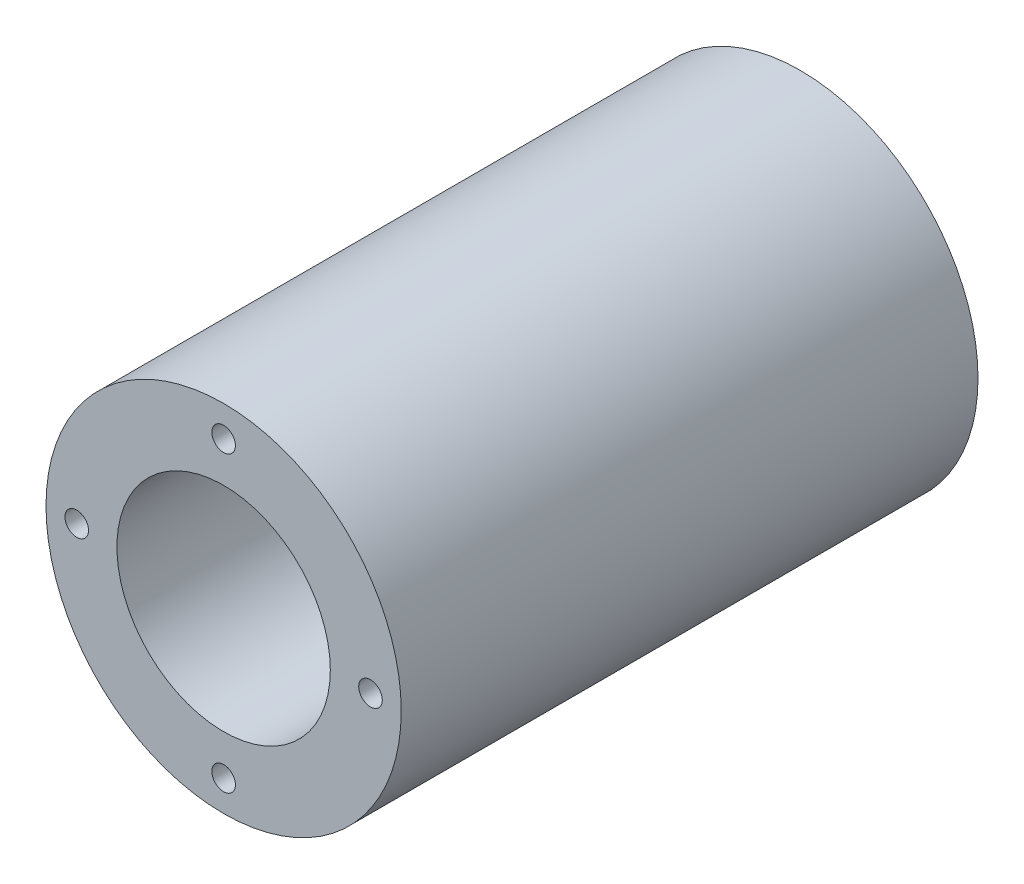
SolidWorks part; units mm, degrees
material "6061-T6 (SS)"
ref_plane "Front Plane" through (0, 0, 0) normal (0, 0, 1) x (1, 0, 0)
ref_plane "Top Plane" through (0, 0, 0) normal (0, 1, 0) x (1, 0, 0)
ref_plane "Right Plane" through (0, 0, 0) normal (1, 0, 0) x (0, 0, -1)
sketch "Sketch Spindle Skeleton" plane through (0, 0, 0) normal (1, 0, 0) x (0, 0, -1)
  line L0 (-119.6, -9.5) -> (-164, -9.5)
  line L5 (-1000, 0) -> (49000, 0)
  line L6 (0, -9.5) -> (0, 9.5)
  line L13 (0, 9.5) -> (-46.4, 9.5)
  line L26 (-46.4, 9.5) -> (-46.4, 14)
  line L27 (-46.4, 14) -> (-119.6, 14)
  line L32 (-119.6, 14) -> (-119.6, 9.5)
  line L34 (-180, 7) -> (-180, -7)
  line L36 (-119.6, -9.5) -> (-119.6, -14)
  line L37 (-119.6, -14) -> (-46.4, -14)
  line L38 (-46.4, -14) -> (-46.4, -9.5)
  line L39 (0, -9.5) -> (-46.4, -9.5)
  line L40 (-24.625, 37.6491) -> (-15.625, 37.6491)
  line L41 (-136.2, 22.6187) -> (-119.6, 22.6187)
  line L42 (-136.2, 22.6187) -> (-136.2, -22.6187)
  line L43 (-136.2, -22.6187) -> (-119.6, -22.6187)
  line L44 (-119.6, 22.6187) -> (-119.6, -22.6187)
  line L45 (-136.2, 22.6187) -> (-119.6, -22.6187) construction
  line L46 (-136.2, -22.6187) -> (-119.6, 22.6187) construction
  line L47 (-29.8, 22.6187) -> (-46.4, 22.6187)
  line L48 (-29.8, 22.6187) -> (-29.8, -22.6187)
  line L49 (-29.8, -22.6187) -> (-46.4, -22.6187)
  line L50 (-46.4, 22.6187) -> (-46.4, -22.6187)
  line L51 (-29.8, 22.6187) -> (-46.4, -22.6187) construction
  line L52 (-29.8, -22.6187) -> (-46.4, 22.6187) construction
  line L59 (-15.625, 37.6491) -> (-15.625, -37.6491)
  line L60 (-15.625, -37.6491) -> (-24.625, -37.6491)
  line L61 (-24.625, -22.6187) -> (-26.625, -22.6187)
  line L62 (-26.625, -22.6187) -> (-26.625, -12.5)
  line L63 (-26.625, -12.5) -> (-24.625, -12.5)
  line L64 (-24.625, -12.5) -> (-24.625, 12.5)
  line L65 (-24.625, 12.5) -> (-26.625, 12.5)
  line L66 (-26.625, 12.5) -> (-26.625, 22.6187)
  line L67 (-26.625, 22.6187) -> (-24.625, 22.6187)
  line L68 (-24.625, 22.6187) -> (-24.625, 37.6491)
  line L69 (-24.625, -22.6187) -> (-24.625, -37.6491)
  line L71 (-147.884, 37.6491) -> (-25.625, 37.6491)
  line L72 (-147.884, 37.6491) -> (-147.884, -37.6491)
  line L73 (-147.884, -37.6491) -> (-25.625, -37.6491)
  line L74 (-25.625, 37.6491) -> (-25.625, -37.6491)
  line L75 (-147.884, 37.6491) -> (-25.625, -37.6491) construction
  line L76 (-147.884, -37.6491) -> (-25.625, 37.6491) construction
  line L77 (-164, -9.5) -> (-164, -7)
  line L78 (-164, -7) -> (-180, -7)
  line L79 (-119.6, 9.5) -> (-164, 9.5)
  line L80 (-164, 7) -> (-180, 7)
  line L81 (-164, 9.5) -> (-164, 7)
  line L82 (-141.8, 9.5) -> (-141.8, -9.5) construction
  line L83 (-23.2, 9.5) -> (-23.2, -9.5) construction
  line L96 (-147.884, 37.6492) -> (-156.884, 37.6492)
  line L98 (-147.884, -37.6491) -> (-156.884, -37.6491)
  line L99 (-156.884, 37.6492) -> (-156.884, -37.6491)
  line L110 (-147.884, 37.6492) -> (-147.884, -37.6491)
  point P3 (0, 0)
  point P18 (-127.9, 0)
  point P24 (-38.1, 0)
  point P29 (-86.7545, 0)
  point P48 (-15.625, 31.1339)
  point P70 (-156.884, 31.1339)
sketch "Sketch1" plane through (0, 0, 0) normal (1, 0, 0) x (0, 0, -1)
  line L0 (-25.625, 37.6491) -> (-25.625, -37.6491) construction
  line L1 (-147.884, -37.6491) -> (-25.625, -37.6491) construction
  line L2 (-147.884, 37.6491) -> (-147.884, -37.6491) construction
  line L3 (-147.884, 37.6491) -> (-25.625, 37.6491) construction
  line L4 (-25.625, 37.6491) -> (-25.625, -37.6491)
  line L5 (-147.884, -37.6491) -> (-25.625, -37.6491)
  line L6 (-147.884, 37.6491) -> (-147.884, -37.6491)
  line L7 (-147.884, 37.6491) -> (-25.625, 37.6491)
  line L9 (-29.8, 22.6187) -> (-46.4, 22.6187) construction
  line L10 (-147.884, 22.6187) -> (-25.625, 22.6187)
  line L15 (-147.884, 0) -> (-25.625, 0) construction
revolve "Revolve1" add sketch "Sketch1" angle 360 about L15 region at (0, 30.1339, 86.7545)
sketch "Back Hole Top Location" plane through (0, 0, 25.625) normal (0, 0, -1) x (-1, 0, 0)
  point P9 (0, 31.1339)
hole_wizard "M6x1.0 Tapped Hole3" positions "Sketch8" profile "Sketch9" tap size "M6x1.0" standard "ANSI Metric"
sketch "Sketch8" plane through (0, 0, 25.625) normal (0, 0, -1) x (-1, 0, 0)
  point P0 (0, 31.1339)
sketch "Sketch9" plane through (0, 31.1339, 25.625) normal (1, 0, 0) x (0, 1, 0)
  line L0 (0, 0) -> (0, 16.5022)
  line L1 (0, 16.5022) -> (2.5, 15)
  line L2 (2.5, 15) -> (2.5, 0)
  line L5 (2.5, 0) -> (0, 0)
  line L10 (0, 16.5022) -> (-2.5, 15) construction
  line L11 (0, -6.35) -> (0, 107.95) construction
  dimension "Tap Drill Dia." = 5
  dimension "Tap Drill Depth" = 15
  dimension "Drill Angle" = 118
pattern_circular "BackFacePattern" count 6 over 360 about axis through (0, 0, 1000) along (0, 0, -1) of "M6x1.0 Tapped Hole3"
ref_plane "Midplane" through (0, 0, 86.7545) normal (0, 0, -1) x (-1, 0, 0)
sketch "Front Hole Top Location" plane through (0, 0, 147.884) normal (0, 0, 1) x (1, 0, 0)
  point P0 (0, 31.1339)
hole_wizard "M6x1.0 Tapped Hole2" positions "Sketch5" profile "Sketch6" tap size "M6x1.0" standard "ANSI Metric"
sketch "Sketch5" plane through (0, 0, 147.884) normal (0, 0, 1) x (1, 0, 0)
  point P0 (0, 31.1339)
sketch "Sketch6" plane through (0, 31.1339, 147.884) normal (1, 0, 0) x (0, -1, 0)
  line L0 (0, 0) -> (0, 16.5022)
  line L1 (0, 16.5022) -> (2.5, 15)
  line L2 (2.5, 15) -> (2.5, 0)
  line L5 (2.5, 0) -> (0, 0)
  line L10 (0, 16.5022) -> (-2.5, 15) construction
  line L11 (0, -6.35) -> (0, 107.95) construction
  dimension "Tap Drill Dia." = 5
  dimension "Tap Drill Depth" = 15
  dimension "Drill Angle" = 118
pattern_circular "FrontFacePattern" count 4 over 360 about axis through (0, 0, 1000) along (0, 0, -1) of "M6x1.0 Tapped Hole2"
sketch "Sketch7" plane through (0, 0, 25.625) normal (0, 0, -1) x (-1, 0, 0)
  circle A0 centre (0, 0) radius 26.9875
  circle A1 centre (0, 0) radius 24.6062
  dimension "D1" = 53.975
  dimension "D2" = 49.2125
extrude "Cut-Extrude1" cut sketch "Sketch7" against normal blind 0.5
